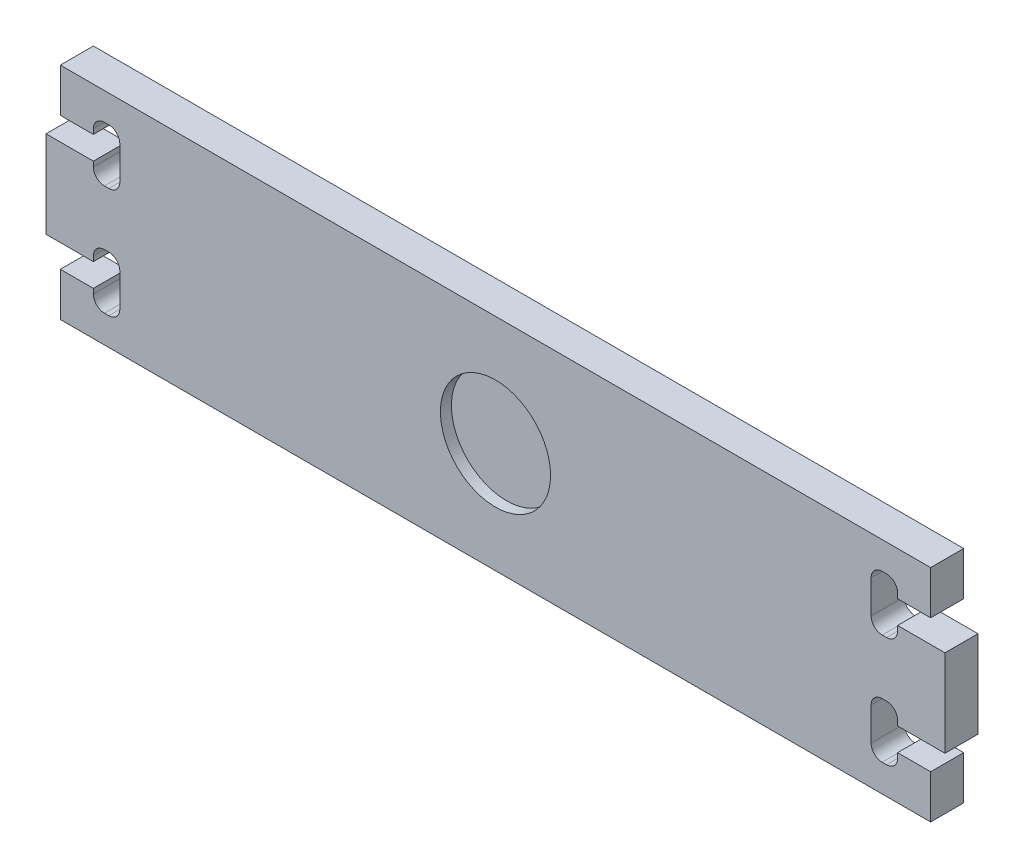
SolidWorks part; units mm, degrees
ref_plane "Front Plane" through (0, 0, 0) normal (0, 0, 1) x (1, 0, 0)
ref_plane "Top Plane" through (0, 0, 0) normal (0, 1, 0) x (1, 0, 0)
ref_plane "Right Plane" through (0, 0, 0) normal (1, 0, 0) x (0, 0, -1)
sketch "Sketch1" plane through (0, 0, 0) normal (0, 0, 1) x (1, 0, 0)
  line L0 (-39.5, 0) -> (39.5, 0) construction
  line L1 (-39.5, 10) -> (39.5, 10)
  line L2 (-39.5, 10) -> (-39.5, -10)
  line L3 (-39.5, -10) -> (39.5, -10)
  line L4 (39.5, 10) -> (39.5, -10)
  line L5 (-39.5, 10) -> (39.5, -10) construction
  line L6 (-39.5, -10) -> (39.5, 10) construction
  line L7 (0, 10) -> (0, -10) construction
  line L9 (-40.8, -3.95) -> (-39.5, -3.95)
  line L10 (-40.8, -3.95) -> (-40.8, 3.95)
  line L11 (-40.8, 3.95) -> (-39.5, 3.95)
  line L12 (-39.5, -3.95) -> (-39.5, 3.95)
  line L13 (-40.8, -3.95) -> (-39.5, 3.95) construction
  line L14 (-40.8, 3.95) -> (-39.5, -3.95) construction
  line L16 (40.8, 3.95) -> (39.5, 3.95)
  line L17 (40.8, -3.95) -> (40.8, 3.95)
  line L18 (40.8, -3.95) -> (39.5, -3.95)
  line L19 (-39.5, 5) -> (39.5, 5) construction
  line L20 (-35.3, 7.5) -> (-35.3, 2.5) construction
  line L21 (-36.5, 3.95) -> (-39.5, 3.95)
  line L22 (-36.5, 3.95) -> (-36.5, 6.05)
  line L23 (-36.5, 6.05) -> (-39.5, 6.05)
  line L24 (-39.5, 3.95) -> (-39.5, 6.05)
  line L25 (-36.5, 3.95) -> (-39.5, 6.05) construction
  line L26 (-36.5, 6.05) -> (-39.5, 3.95) construction
  line L27 (-34.1, 7.5) -> (-36.5, 7.5)
  line L28 (-34.1, 7.5) -> (-34.1, 2.5)
  line L29 (-34.1, 2.5) -> (-36.5, 2.5)
  line L30 (-36.5, 7.5) -> (-36.5, 2.5)
  line L31 (-34.1, 7.5) -> (-36.5, 2.5) construction
  line L32 (-34.1, 2.5) -> (-36.5, 7.5) construction
  line L33 (-34.1, -7.5) -> (-36.5, -7.5)
  line L34 (-34.1, -7.5) -> (-34.1, -2.5)
  line L35 (-34.1, -2.5) -> (-36.5, -2.5)
  line L36 (-36.5, -7.5) -> (-36.5, -2.5)
  line L37 (-36.5, -3.95) -> (-39.5, -3.95)
  line L38 (-36.5, -6.05) -> (-39.5, -6.05)
  line L39 (36.5, 3.95) -> (39.5, 3.95)
  line L40 (36.5, 6.05) -> (39.5, 6.05)
  line L41 (36.5, 7.5) -> (36.5, 2.5)
  line L42 (34.1, 7.5) -> (36.5, 7.5)
  line L43 (34.1, 7.5) -> (34.1, 2.5)
  line L44 (34.1, 2.5) -> (36.5, 2.5)
  line L45 (34.1, -2.5) -> (36.5, -2.5)
  line L46 (34.1, -7.5) -> (34.1, -2.5)
  line L47 (34.1, -7.5) -> (36.5, -7.5)
  line L48 (36.5, -7.5) -> (36.5, -2.5)
  line L49 (36.5, -6.05) -> (39.5, -6.05)
  line L50 (36.5, -3.95) -> (39.5, -3.95)
  point P0 (0, 0)
  point P10 (-40.15, 0)
  point P15 (-38, 5)
  point P35 (-35.3, 5)
  dimension "D1" = 79
  dimension "D2" = 20
  dimension "D4" = 1.3
  dimension "D7" = 5
  dimension "D8" = 2.1
  dimension "D9" = 3
  dimension "D10" = 2.4
  dimension "D11" = 5
extrude "Base shape" add sketch "Sketch1" along normal blind 3 contours L4 L1 L2 L3 | L9 L2 L11 L10 | L16 L4 L18 L17 region at (0, 0, 0) region at (-40.15, 0, 0) region at (40.15, 0, 0)
sketch "Sketch2" plane through (0, 0, 3) normal (0, 0, 1) x (1, 0, 0)
  circle A0 centre (0, 0) radius 5
  dimension "D1" = 10
extrude "Forward cut (temp)" cut sketch "Sketch2" against normal blind 1
fillet "Fillet1" radius 1 16 edges at (36.5, -7.5, 1.5) (36.5, 2.5, 1.5) (34.1, 2.5, 1.5) (34.1, -7.5, 1.5) (36.5, -2.5, 1.5) (36.5, 7.5, 1.5) (34.1, -2.5, 1.5) (34.1, 7.5, 1.5) (-36.5, -2.5, 1.5) (-34.1, -2.5, 1.5) (-34.1, -7.5, 1.5) (-36.5, -7.5, 1.5) (-36.5, 2.5, 1.5) (-34.1, 2.5, 1.5) (-34.1, 7.5, 1.5) (-36.5, 7.5, 1.5)
sketch "Sketch3" plane through (-40.8, 0, 0) normal (-1, 0, 0) x (0, 0, 1)
  line L0 (0, 6.05) -> (3, 3.95) construction
  line L1 (0, 6.05) -> (3, 6.05)
  line L2 (0, 6.05) -> (0, 3.95)
  line L3 (0, 3.95) -> (3, 3.95)
  line L4 (3, 6.05) -> (3, 3.95)
  line L5 (0, -3.95) -> (3, -6.05) construction
  line L6 (0, -3.95) -> (3, -3.95)
  line L7 (0, -3.95) -> (0, -6.05)
  line L8 (0, -6.05) -> (3, -6.05)
  line L9 (3, -3.95) -> (3, -6.05)
  point P6 (1.5, 5)
  point P13 (1.5, -5)
ref_axis "Tap axis top" through (-53.7846, 5, 1.5) along (1, 0, 0)
ref_axis "Tap axis bottom" through (-54.2844, -5, 1.5) along (1, 0, 0)
